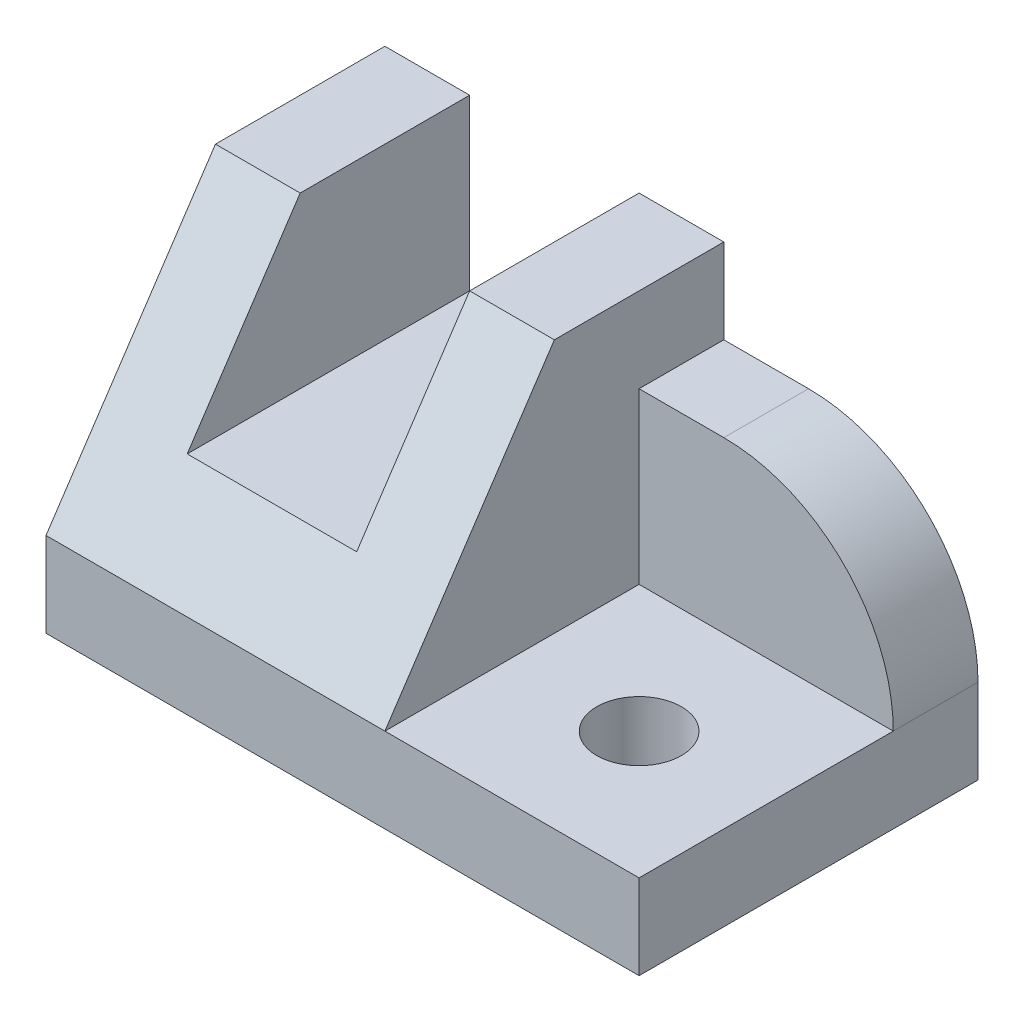
SolidWorks part; units mm, degrees
ref_plane "前基準面" through (0, 0, 0) normal (0, 0, 1) x (1, 0, 0)
ref_plane "上基準面" through (0, 0, 0) normal (0, 1, 0) x (1, 0, 0)
ref_plane "右基準面" through (0, 0, 0) normal (1, 0, 0) x (0, 0, -1)
sketch "草圖1" plane through (0, 0, 0) normal (0, 1, 0) x (1, 0, 0)
  line L1 (-17.5, -10) -> (17.5, -10)
  line L2 (-17.5, -10) -> (-17.5, 10)
  line L3 (-17.5, 10) -> (17.5, 10)
  line L4 (17.5, -10) -> (17.5, 10)
  line L5 (-17.5, -10) -> (17.5, 10) construction
  line L6 (-17.5, 10) -> (17.5, -10) construction
  line L7 (-17.5, 10) -> (2.5, 10)
  line L8 (-17.5, 10) -> (-17.5, -10)
  line L9 (-17.5, -10) -> (2.5, -10)
  line L10 (2.5, 10) -> (2.5, -10)
  line L11 (2.5, 10) -> (17.5, 10)
  line L12 (2.5, 10) -> (2.5, 5)
  line L13 (2.5, 5) -> (17.5, 5)
  line L14 (17.5, 10) -> (17.5, 5)
  circle A0 centre (10, -2.5) radius 2.5
  point P0 (0, 0)
  point P14 (17.5, -2.4781)
  dimension "D5" = 5
  dimension "D1" = 35
  dimension "D2" = 20
  dimension "D3" = 5
  dimension "D4" = 20
  dimension "D6" = 7.5
  dimension "D7" = 7.5
extrude "填料-伸長1" add sketch "草圖1" along normal blind 5 contours L13 L10 L1 L4 A0 region at (2.7121, 0, 2.5)
extrude "填料-伸長2" add sketch "草圖1<3>" along normal blind 15 contours L10 L13 L4 L3 region at (10, 0, -7.5)
sketch "草圖1<3>" plane through (0, 0, 0) normal (0, 1, 0) x (1, 0, 0) same geometry as "草圖1"
extrude "填料-伸長3" add sketch "草圖1<4>" along normal blind 20 contours L10 L3 L2 L1 region at (-7.5, 0, 0)
sketch "草圖1<4>" plane through (0, 0, 0) normal (0, 1, 0) x (1, 0, 0) same geometry as "草圖1"
sketch "草圖2" plane through (2.5, 0, 0) normal (1, 0, 0) x (0, 0, -1)
  line L0 (-10, 5) -> (0, 20)
  line L1 (10, 20) -> (-10, 20) construction
  line L2 (0, 20) -> (-10, 20)
  line L3 (-10, 20) -> (-10, 5)
  dimension "D1" = 10
extrude "除料-伸長1" cut sketch "草圖2" against normal blind 20
sketch "草圖3" plane through (0, 0, -10) normal (0, 0, -1) x (-1, 0, 0)
  line L0 (17.5, 20) -> (-2.5, 20) construction
  line L1 (2.5, 20) -> (12.5, 20)
  line L2 (2.5, 20) -> (2.5, 10)
  line L3 (2.5, 10) -> (12.5, 10)
  line L4 (12.5, 20) -> (12.5, 10)
  line L5 (17.5, 20) -> (17.5, 0) construction
  line L6 (-2.5, 20) -> (-2.5, 15) construction
  dimension "D1" = 10
  dimension "D2" = 5
  dimension "D3" = 5
extrude "除料-伸長2" cut sketch "草圖3" against normal blind 20
fillet "圓角1" radius 10 1 edges at (17.5, 15, -7.5)
